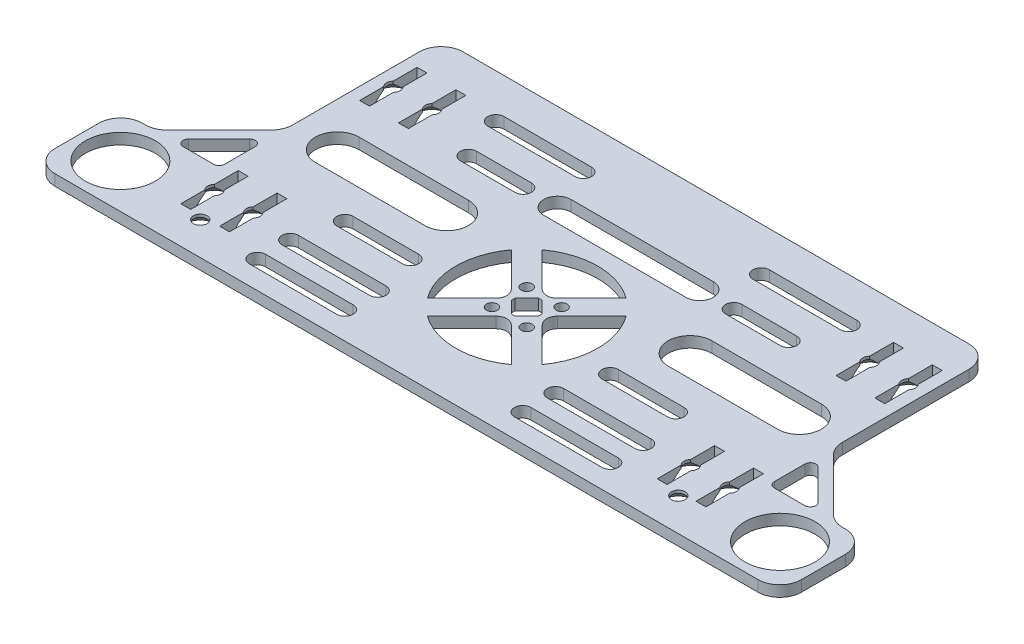
SolidWorks part; units mm, degrees
ref_plane "前视基准面" through (0, 0, 0) normal (0, 0, 1) x (1, 0, 0)
ref_plane "上视基准面" through (0, 0, 0) normal (0, 1, 0) x (1, 0, 0)
ref_plane "右视基准面" through (0, 0, 0) normal (1, 0, 0) x (0, 0, -1)
sketch "草图1" plane through (0, 0, 0) normal (0, 1, 0) x (1, 0, 0)
  line L0 (0, 0) -> (0, 46.1677) construction
  line L1 (-68.25, 0) -> (68.25, 0)
  line L2 (68.25, 0) -> (68.25, 16)
  line L8 (-68.25, 0) -> (-68.25, 16)
  line L9 (68.25, 16) -> (62.0784, 16)
  line L11 (50.25, 16) -> (50.25, 25)
  line L12 (50.25, 56.6) -> (-50.25, 56.6)
  line L13 (-50.25, 16) -> (-50.25, 25)
  line L14 (-68.25, 16) -> (-62.0784, 16)
  line L15 (59.25, 16) -> (50.25, 25)
  line L16 (62.0784, 16) -> (50.25, 27.8284)
  line L17 (50.25, 27.8284) -> (50.25, 56.6)
  line L18 (59.25, 16) -> (50.25, 16)
  line L19 (-62.0784, 16) -> (-50.25, 27.8284)
  line L20 (-59.25, 16) -> (-50.25, 25)
  line L21 (-59.25, 16) -> (-50.25, 16)
  line L22 (-50.25, 27.8284) -> (-50.25, 56.6)
  line L23 (0, 22) -> (7.4008, 22) construction
  line L24 (0, 22) -> (9.4181, 31.4181) construction
  line L25 (-10.4972, 29.6687) -> (7.6687, 11.5028)
  line L26 (10.4972, 14.3313) -> (-7.6687, 32.4972)
  line L27 (-10.4972, 14.3313) -> (7.6687, 32.4972)
  line L28 (10.4972, 29.6687) -> (-7.6687, 11.5028)
  line L29 (46.2, 17.25) -> (48, 6.75) construction
  line L30 (46.2, 17.25) -> (48, 17.25)
  line L31 (46.2, 17.25) -> (46.2, 6.75)
  line L32 (46.2, 6.75) -> (48, 6.75)
  line L33 (48, 17.25) -> (48, 6.75)
  line L34 (-46.2, 6.75) -> (-48, 6.75)
  line L35 (-48, 17.25) -> (-48, 6.75)
  line L36 (-46.2, 17.25) -> (-48, 17.25)
  line L37 (-46.2, 17.25) -> (-46.2, 6.75)
  line L38 (47.1, 0) -> (47.1, 56.6) construction
  line L39 (46.2, 49.95) -> (48, 39.45) construction
  line L40 (46.2, 49.95) -> (48, 49.95)
  line L41 (46.2, 49.95) -> (46.2, 39.45)
  line L42 (46.2, 39.45) -> (48, 39.45)
  line L43 (48, 49.95) -> (48, 39.45)
  line L44 (-46.2, 49.95) -> (-48, 39.45) construction
  line L45 (-46.2, 49.95) -> (-46.2, 39.45)
  line L46 (-46.2, 39.45) -> (-48, 39.45)
  line L47 (-48, 49.95) -> (-48, 39.45)
  line L48 (-46.2, 49.95) -> (-48, 49.95)
  line L49 (39.1, 17.25) -> (40.9, 17.25)
  line L50 (39.1, 17.25) -> (39.1, 6.75)
  line L51 (39.1, 6.75) -> (40.9, 6.75)
  line L52 (40.9, 17.25) -> (40.9, 6.75)
  line L53 (39.1, 49.95) -> (40.9, 49.95)
  line L54 (39.1, 49.95) -> (39.1, 39.45)
  line L55 (39.1, 39.45) -> (40.9, 39.45)
  line L56 (40.9, 49.95) -> (40.9, 39.45)
  line L57 (39.1, 49.95) -> (40.9, 39.45)
  line L58 (39.1, 17.25) -> (40.9, 6.75)
  line L59 (40, 56.6) -> (40, 0) construction
  line L60 (-39.1, 17.25) -> (-39.1, 6.75)
  line L61 (-39.1, 6.75) -> (-40.9, 6.75)
  line L62 (-40.9, 17.25) -> (-40.9, 6.75)
  line L63 (-39.1, 17.25) -> (-40.9, 17.25)
  line L64 (-39.1, 49.95) -> (-39.1, 39.45)
  line L65 (-39.1, 39.45) -> (-40.9, 39.45)
  line L66 (-40.9, 49.95) -> (-40.9, 39.45)
  line L67 (-39.1, 49.95) -> (-40.9, 49.95)
  line L68 (-47.1, 0) -> (-47.1, 56.6) construction
  line L69 (-40, 56.6) -> (-40, 0) construction
  line L70 (-13, 40.6) -> (13, 40.6) construction
  line L71 (-13, 43.1) -> (13, 43.1)
  line L72 (-13, 38.1) -> (13, 38.1)
  circle A2 centre (60.3, 8) radius 6.4
  circle A3 centre (-60.3, 8) radius 6.4
  circle A4 centre (0, 22) radius 4.5 construction
  circle A5 centre (3.182, 25.182) radius 1
  circle A6 centre (3.182, 18.818) radius 1
  circle A7 centre (-3.182, 18.818) radius 1
  circle A8 centre (-3.182, 25.182) radius 1
  circle A9 centre (0, 22) radius 13
  circle A11 centre (0, 22) radius 2.5
  arc A12 (-13, 43.1) -> (-13, 38.1) centre (-13, 40.6) ccw
  arc A13 (13, 38.1) -> (13, 43.1) centre (13, 40.6) ccw
  circle A14 centre (43.7, 6) radius 1
  circle A15 centre (-43.7, 6) radius 1
  point P3 (0, 56.6)
  point P18 (0, 0)
  point P19 (68.25, 8)
  point P26 (0, 22)
  point P55 (47.1, 12)
  point P66 (47.1, 44.7)
  point P67 (48, 44.7)
  point P68 (48, 12)
  point P85 (40, 44.7)
  point P100 (0, 40.6)
  dimension "D1" = 12.8
  dimension "D5" = 100.5
  dimension "D12" = 9
  dimension "D13" = 2
  dimension "D15" = 26
  dimension "D16" = 2
  dimension "D17" = 5
  dimension "D31" = 16
  dimension "D33" = 2
  dimension "D2" = 120.6
  dimension "D3" = 136.5
  dimension "D4" = 16
  dimension "D6" = 45
  dimension "D7" = 2
  dimension "D8" = 9
  dimension "D9" = 1.8
  dimension "D10" = 56.6
  dimension "D11" = 22
  dimension "D18" = 4
  dimension "D19" = 10.5
  dimension "D20" = 12
  dimension "D21" = 96
  dimension "D22" = 32.7
  dimension "D23" = 10.5
  dimension "D24" = 1.8
  dimension "D25" = 10.5
  dimension "D26" = 1.8
  dimension "D27" = 10.5
  dimension "D28" = 1.8
  dimension "D29" = 80
  dimension "D30" = 2.5
  dimension "D32" = 26
  dimension "D34" = 87.4
  dimension "D35" = 6
  dimension "D14" = 4
extrude "凸台-拉伸1" add sketch "草图1" along normal blind 2 contours L22 L19 L14 L8 L1 L2 L9 L16 L17 L12 A3 A2 L67 L64 L65 L66 L63 L60 L61 L62 L48 L45 L46 L47 L21 L20 L13 L15 L18 L11 L30 L33 L32 L31 L36 L37 L34 L35 L40 L43 L42 | A11 L25 L27 A9 L28 A7 | A11 L28 L25 A9 L26 A6 | A11 L26 L28 A9 L27 A5 | A11 L27 L26 A9 L25 A8 | L26 A11 | A11 L26 L27 | A11 L27 L25 | A11 L25 L28 | A11 L28 L26 | L28 A11 | L25 A11 | L27 A11 region at (-66.7723, 0, -8) region at (-5.548, 0, -27.548) region at (-2.604, 0, -22) region at (-5.548, 0, -16.452) region at (-1.5569, 0, -20.4431) region at (-1.5569, 0, -23.5569) region at (5.548, 0, -27.548) region at (0, 0, -24.604) region at (0, 0, -19.396) region at (1.5569, 0, -23.5569) region at (5.548, 0, -16.452) region at (1.5569, 0, -20.4431) region at (2.604, 0, -22)
fillet "圆角1" radius 2 4 edges at (0, 1, -24.8284) (-2.8284, 1, -22) (0, 1, -19.1716) (2.8284, 1, -22)
fillet "圆角2" radius 4 10 edges at (62.0784, 1, -16) (50.25, 1, -27.8284) (-62.0784, 1, -16) (-50.25, 1, -27.8284) (-50.25, 1, -56.6) (50.25, 1, -56.6) (68.25, 1, -16) (68.25, 1, 0) (-68.25, 1, -16) (-68.25, 1, 0)
fillet "圆角3" radius 1 6 edges at (-50.25, 1, -16) (-59.25, 1, -16) (-50.25, 1, -25) (50.25, 1, -16) (50.25, 1, -25) (59.25, 1, -16)
hole_wizard "M2.5 平头机械螺钉的锥形沉头孔3" positions "草图8" profile "草图9" countersink size "M2.5" standard "ANSI Metric" end condition through all
sketch "草图8" plane through (0, 0, 0) normal (0, -1, 0) x (-1, 0, 0)
  point P0 (-47.1, 44.7)
  point P2 (-40, 44.7)
  point P4 (40, 44.7)
  point P6 (47.1, 44.7)
  point P8 (47.1, 12)
  point P10 (43.7, 6)
  point P13 (40, 12)
  point P15 (-40, 12)
  point P16 (-43.7, 6)
  point P19 (-47.1, 12)
sketch "草图9" plane through (47.1, 0, -44.7) normal (1, 0, 0) x (0, 0, -1)
  line L0 (0, 0) -> (0, 2)
  line L1 (0, 2) -> (1.25, 2)
  line L2 (1.25, 2) -> (1.25, 1.5)
  line L3 (1.25, 1.5) -> (2.75, 0)
  line L5 (2.75, 0) -> (0, 0)
  line L6 (-1.25, 1.5) -> (-2.75, 0) construction
  line L11 (0, -6.35) -> (0, 107.95) construction
  dimension "通孔孔直径" = 2.5
  dimension "通孔孔深度" = 2
  dimension "近端锥形沉头孔直径" = 5.5
  dimension "近端锥形沉头孔角度" = 90
sketch "草图10" plane through (0, 0, 0) normal (0, -1, 0) x (1, 0, 0)
  line L0 (0, 0) -> (0, -49.8475) construction
  line L1 (22.25, -29.6) -> (42.25, -29.6) construction
  line L2 (22.25, -25.6) -> (42.25, -25.6)
  line L3 (22.25, -33.6) -> (42.25, -33.6)
  line L4 (46.25, -56.6) -> (-46.25, -56.6) construction
  line L5 (50.25, -29.4853) -> (50.25, -52.6) construction
  line L6 (-22.25, -29.6) -> (-42.25, -29.6) construction
  line L7 (-22.25, -25.6) -> (-42.25, -25.6)
  line L8 (-22.25, -33.6) -> (-42.25, -33.6)
  line L9 (18.25, -19) -> (30.25, -19) construction
  line L10 (18.25, -17.5) -> (30.25, -17.5)
  line L11 (18.25, -20.5) -> (30.25, -20.5)
  line L12 (16.25, -11) -> (32.25, -11) construction
  line L13 (16.25, -9.5) -> (32.25, -9.5)
  line L14 (16.25, -12.5) -> (32.25, -12.5)
  line L15 (16.25, -5) -> (32.25, -5) construction
  line L16 (16.25, -3.5) -> (32.25, -3.5)
  line L17 (16.25, -6.5) -> (32.25, -6.5)
  line L18 (19.25, -40.6) -> (29.25, -40.6) construction
  line L19 (19.25, -39.1) -> (29.25, -39.1)
  line L20 (19.25, -42.1) -> (29.25, -42.1)
  line L21 (16.25, -48.6) -> (32.25, -48.6) construction
  line L22 (16.25, -47.1) -> (32.25, -47.1)
  line L23 (16.25, -50.1) -> (32.25, -50.1)
  line L24 (-64.25, 0) -> (64.25, 0) construction
  line L25 (-16.25, -5) -> (-32.25, -5) construction
  line L26 (-16.25, -3.5) -> (-32.25, -3.5)
  line L27 (-16.25, -6.5) -> (-32.25, -6.5)
  line L28 (-16.25, -11) -> (-32.25, -11) construction
  line L29 (-16.25, -9.5) -> (-32.25, -9.5)
  line L30 (-16.25, -12.5) -> (-32.25, -12.5)
  line L31 (-18.25, -19) -> (-30.25, -19) construction
  line L32 (-18.25, -17.5) -> (-30.25, -17.5)
  line L33 (-18.25, -20.5) -> (-30.25, -20.5)
  line L34 (-16.25, -48.6) -> (-32.25, -48.6) construction
  line L35 (-16.25, -47.1) -> (-32.25, -47.1)
  line L36 (-16.25, -50.1) -> (-32.25, -50.1)
  line L37 (-19.25, -40.6) -> (-29.25, -40.6) construction
  line L38 (-19.25, -39.1) -> (-29.25, -39.1)
  line L39 (-19.25, -42.1) -> (-29.25, -42.1)
  arc A0 (22.25, -25.6) -> (22.25, -33.6) centre (22.25, -29.6) ccw
  arc A1 (42.25, -33.6) -> (42.25, -25.6) centre (42.25, -29.6) ccw
  arc A2 (-22.25, -25.6) -> (-22.25, -33.6) centre (-22.25, -29.6) cw
  arc A3 (-42.25, -33.6) -> (-42.25, -25.6) centre (-42.25, -29.6) cw
  arc A4 (18.25, -17.5) -> (18.25, -20.5) centre (18.25, -19) ccw
  arc A5 (30.25, -20.5) -> (30.25, -17.5) centre (30.25, -19) ccw
  arc A6 (16.25, -9.5) -> (16.25, -12.5) centre (16.25, -11) ccw
  arc A7 (32.25, -12.5) -> (32.25, -9.5) centre (32.25, -11) ccw
  arc A8 (16.25, -3.5) -> (16.25, -6.5) centre (16.25, -5) ccw
  arc A9 (32.25, -6.5) -> (32.25, -3.5) centre (32.25, -5) ccw
  arc A10 (19.25, -39.1) -> (19.25, -42.1) centre (19.25, -40.6) ccw
  arc A11 (29.25, -42.1) -> (29.25, -39.1) centre (29.25, -40.6) ccw
  arc A12 (16.25, -47.1) -> (16.25, -50.1) centre (16.25, -48.6) ccw
  arc A13 (32.25, -50.1) -> (32.25, -47.1) centre (32.25, -48.6) ccw
  arc A14 (-16.25, -3.5) -> (-16.25, -6.5) centre (-16.25, -5) cw
  arc A15 (-32.25, -6.5) -> (-32.25, -3.5) centre (-32.25, -5) cw
  arc A16 (-16.25, -9.5) -> (-16.25, -12.5) centre (-16.25, -11) cw
  arc A17 (-32.25, -12.5) -> (-32.25, -9.5) centre (-32.25, -11) cw
  arc A18 (-18.25, -17.5) -> (-18.25, -20.5) centre (-18.25, -19) cw
  arc A19 (-30.25, -20.5) -> (-30.25, -17.5) centre (-30.25, -19) cw
  arc A20 (-16.25, -47.1) -> (-16.25, -50.1) centre (-16.25, -48.6) cw
  arc A21 (-32.25, -50.1) -> (-32.25, -47.1) centre (-32.25, -48.6) cw
  arc A22 (-19.25, -39.1) -> (-19.25, -42.1) centre (-19.25, -40.6) cw
  arc A23 (-29.25, -42.1) -> (-29.25, -39.1) centre (-29.25, -40.6) cw
  point P6 (32.25, -29.6)
  point P16 (24.25, -19)
  point P19 (-32.25, -29.6)
  point P30 (24.25, -11)
  point P37 (24.25, -5)
  point P44 (24.25, -40.6)
  point P51 (24.25, -48.6)
  point P62 (-24.25, -5)
  point P69 (-24.25, -11)
  point P76 (-24.25, -19)
  point P83 (-24.25, -48.6)
  point P90 (-24.25, -40.6)
  dimension "D1" = 4
  dimension "D2" = 23
  dimension "D3" = 8
  dimension "D4" = 20
  dimension "D5" = 16
  dimension "D6" = 16
  dimension "D7" = 12
  dimension "D8" = 10
  dimension "D9" = 16
  dimension "D10" = 3
  dimension "D11" = 3
  dimension "D12" = 3
  dimension "D13" = 3
  dimension "D14" = 3
  dimension "D15" = 6
  dimension "D16" = 8
  dimension "D17" = 5
  dimension "D18" = 26
  dimension "D19" = 8
  dimension "D20" = 8
extrude "切除-拉伸1" cut sketch "草图10" against normal up to surface (2 mm away) up to face at (40, 2, -44.7)
